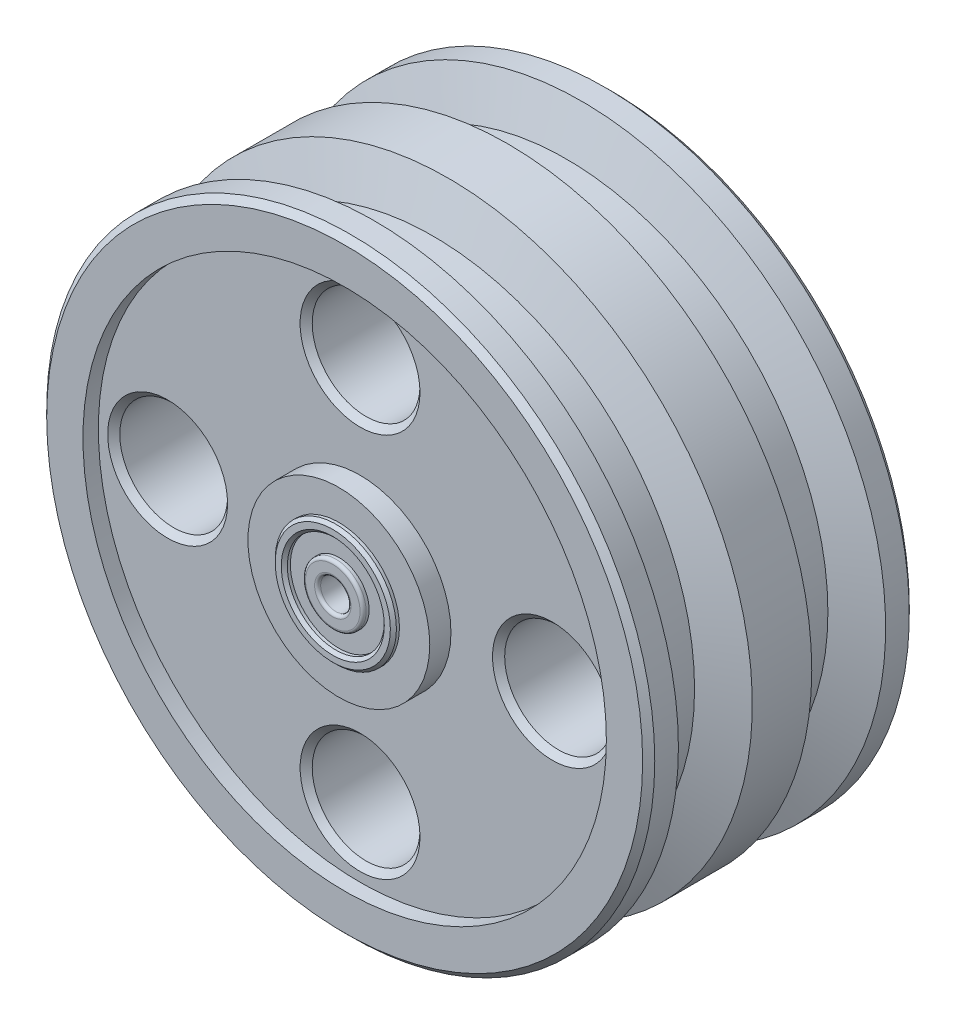
SolidWorks part; units mm, degrees
ref_plane "Front Plane" through (0, 0, 0) normal (0, 0, 1) x (1, 0, 0)
ref_plane "Top Plane" through (0, 0, 0) normal (0, 1, 0) x (1, 0, 0)
ref_plane "Right Plane" through (0, 0, 0) normal (1, 0, 0) x (0, 0, -1)
sketch "Sketch2" plane through (0, 0, 0) normal (0, 0, 1) x (1, 0, 0)
  circle A0 centre (0, 0) radius 50.165
extrude "Boss-Extrude1" add sketch "Sketch2" against normal blind 10 contours A0
ref_plane "Plane1" through (0, 0, -10) normal (0, 0, -1) x (-1, 0, 0)
sketch "Sketch4" plane through (0, 0, -10) normal (0, 0, -1) x (-1, 0, 0)
  circle A0 centre (0, 0) radius 43.18
extrude "Boss-Extrude2" add sketch "Sketch4" along normal blind 2
ref_plane "Plane2" through (0, 0, -12) normal (0, 0, -1) x (-1, 0, 0)
sketch "Sketch5" plane through (0, 0, -12) normal (0, 0, -1) x (-1, 0, 0)
  circle A0 centre (0, 0) radius 50.165
extrude "Boss-Extrude3" add sketch "Sketch5" along normal blind 20
ref_plane "Plane3" through (0, 0, -32) normal (0, 0, -1) x (-1, 0, 0)
sketch "Sketch7" plane through (0, 0, -32) normal (0, 0, -1) x (-1, 0, 0)
  circle A0 centre (0, 0) radius 43.18
extrude "Boss-Extrude4" add sketch "Sketch7" along normal blind 2
ref_plane "Plane4" through (0, 0, -34) normal (0, 0, -1) x (-1, 0, 0)
sketch "Sketch8" plane through (0, 0, -34) normal (0, 0, -1) x (-1, 0, 0)
  circle A0 centre (0, 0) radius 50.165
extrude "Boss-Extrude5" add sketch "Sketch8" along normal blind 10
chamfer "Chamfer1" distance 14 angle 20 1 edges at (50.165, 0, -10) first distance on face at (50.165, 0, -10)
chamfer "Chamfer2" distance 14 angle 20 1 edges at (-50.165, 0, -12) first distance on face at (-50.165, 0, -12)
chamfer "Chamfer4" distance 14 angle 20 1 edges at (-50.165, 0, -32) first distance on face at (-50.165, 0, -32)
chamfer "Chamfer5" distance 14 angle 20 1 edges at (-50.165, 0, -34) first distance on face at (-50.165, 0, -34)
sketch "Sketch9" plane through (0, 0, 0) normal (0, 0, 1) x (1, 0, 0)
  circle A0 centre (0, 0) radius 2.5
ref_plane "Plane5" through (0, 0, 0) normal (0, 0, 1) x (1, 0, 0)
sketch "Sketch13" plane through (0, 0, 0) normal (0, 0, 1) x (1, 0, 0)
  circle A0 centre (0, 0) radius 43.18
extrude "Cut-Extrude3" cut sketch "Sketch13" against normal blind 2.54
ref_plane "Plane7" through (0, 0, -2.54) normal (0, 0, 1) x (1, 0, 0)
sketch "Sketch18" plane through (0, 0, -2.54) normal (0, 0, 1) x (1, 0, 0)
  circle A0 centre (0, 0) radius 15
extrude "Boss-Extrude12" add sketch "Sketch18" along normal blind 3.5
ref_plane "Plane8" through (0, 0, 0.96) normal (0, 0, 1) x (1, 0, 0)
sketch "Sketch19" plane through (0, 0, 0.96) normal (0, 0, 1) x (1, 0, 0)
  circle A0 centre (0, 0) radius 10
extrude "Boss-Extrude13" add sketch "Sketch19" along normal blind 1
ref_plane "Plane9" through (0, 0, 1.96) normal (0, 0, 1) x (1, 0, 0)
sketch "Sketch20" plane through (0, 0, 1.96) normal (0, 0, 1) x (1, 0, 0)
  circle A0 centre (0, 0) radius 8
  circle A1 centre (0, 0) radius 5
extrude "Cut-Extrude4" cut sketch "Sketch20" against normal blind 1
ref_plane "Plane10" through (0, 0, -44) normal (0, 0, -1) x (-1, 0, 0)
sketch "Sketch22" plane through (0, 0, -44) normal (0, 0, -1) x (-1, 0, 0)
  circle A0 centre (0, 0) radius 43.18
  circle A1 centre (0, 0) radius 15
extrude "Cut-Extrude5" cut sketch "Sketch22" against normal blind 2.54 contours A1 | A0
sketch "Sketch23" plane through (0, 0, -44) normal (0, 0, -1) x (-1, 0, 0)
  circle A0 centre (0, 0) radius 15
extrude "Boss-Extrude14" add sketch "Sketch23" along normal blind 1
ref_plane "Plane11" through (0, 0, -45) normal (0, 0, -1) x (-1, 0, 0)
sketch "Sketch24" plane through (0, 0, -45) normal (0, 0, -1) x (-1, 0, 0)
  circle A0 centre (0, 0) radius 10
extrude "Boss-Extrude15" add sketch "Sketch24" along normal blind 1
ref_plane "Plane12" through (0, 0, -46) normal (0, 0, -1) x (-1, 0, 0)
sketch "Sketch25" plane through (0, 0, -46) normal (0, 0, -1) x (-1, 0, 0)
  circle A0 centre (0, 0) radius 8
  circle A1 centre (0, 0) radius 5
extrude "Cut-Extrude6" cut sketch "Sketch25" against normal blind 1
sketch "Sketch26" plane through (0, 0, 1.96) normal (0, 0, 1) x (1, 0, 0)
  circle A0 centre (0, 0) radius 2.5
extrude "Cut-Extrude7" cut sketch "Sketch26" against normal through all
chamfer "Chamfer9" distance 0.5 angle 45 2 edges at (8, 0, 1.96) (10, 0, 1.96)
fillet "Fillet1" radius 0.5 1 edges at (5, 0, 1.96)
fillet "Fillet2" radius 0.5 1 edges at (2.5, 0, 1.96)
chamfer "Chamfer10" distance 0.5 angle 45 2 edges at (-10, 0, -46) (-8, 0, -46)
chamfer "Chamfer11" distance 0.5 angle 45 1 edges at (-5, 0, -46)
fillet "Fillet3" radius 0.5 1 edges at (2.5, 0, -46)
sketch "Sketch29" plane through (0, 0, -44) normal (0, 0, -1) x (-1, 0, 0)
  circle A0 centre (0, 31.75) radius 8.89
  circle A1 centre (31.75, 0) radius 8.89
  circle A2 centre (0, -31.75) radius 8.89
  circle A3 centre (-31.75, 0) radius 8.89
  point P11 (0, 0)
  dimension "D1" = 4
extrude "Cut-Extrude9" cut sketch "Sketch29" against normal through all
chamfer "Chamfer12" distance 1 angle 45 8 edges at (-40.64, 0, -41.46) (-8.89, 31.75, -41.46) (22.86, 0, -41.46) (-8.89, -31.75, -41.46) (8.89, -31.75, -2.54) (-22.86, 0, -2.54) (8.89, 31.75, -2.54) (40.64, 0, -2.54)
chamfer "Chamfer13" distance 1 angle 45 2 edges at (50.165, 0, 0) (-50.165, 0, -44)
